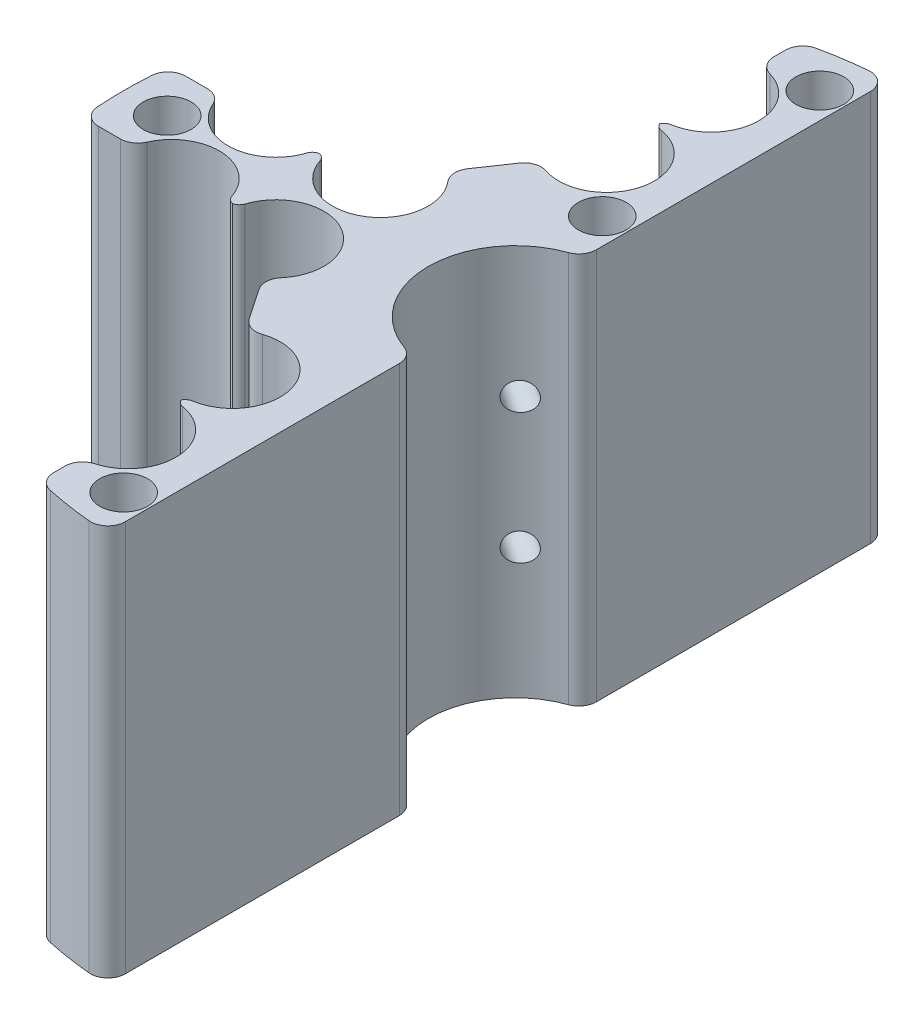
SolidWorks part; units mm, degrees
ref_plane "Front Plane" through (0, 0, 0) normal (0, 0, 1) x (1, 0, 0)
ref_plane "Top Plane" through (0, 0, 0) normal (0, 1, 0) x (1, 0, 0)
ref_plane "Right Plane" through (0, 0, 0) normal (1, 0, 0) x (0, 0, -1)
sketch "Sketch1" plane through (0, 0, 0) normal (0, 1, 0) x (1, 0, 0)
  line L1 (0, 45) -> (47.41, 45)
  line L2 (0, 45) -> (0, -45)
  line L3 (0, -45) -> (47.41, -45)
  line L4 (47.41, 45) -> (47.41, -45)
  line L5 (0, 45) -> (-1, 45)
  line L6 (0, 45) -> (0, -46.0697)
  line L7 (0, -46.0697) -> (-1, -46.0697)
  line L8 (-1, 45) -> (-1, -46.0697)
  circle A0 centre (0, 0) radius 45
  circle A1 centre (0, 0) radius 10
extrude "Boss-Extrude1" add sketch "Sketch1" along normal blind 45 contours A1 L2 A0
sketch "Sketch2" plane through (0, 45, 0) normal (0, 1, 0) x (1, 0, 0)
  circle A0 centre (-40, 0) radius 2.75
  circle A1 centre (-5, 15) radius 2.75
  circle A2 centre (-5, 40) radius 2.75
  circle A3 centre (-5, -40) radius 2.75
extrude "Cut-Extrude1" cut sketch "Sketch2" against normal blind 45
sketch "Sketch3" plane through (0, 45, 0) normal (0, 1, 0) x (1, 0, 0)
  line L0 (-40, 0) -> (-27.5, 0)
  line L1 (-27.5, 0) -> (-27.5, 6)
  line L2 (-27.5, 6) -> (-33.5, 6)
  line L3 (-27.5, 6) -> (-21.5, 6)
  line L4 (-5, 15) -> (-5, 27.5)
  line L5 (-5, 27.5) -> (-11, 27.5)
  line L6 (-11, 27.5) -> (-11, 21.5)
  line L7 (-11, 27.5) -> (-11, 33.5)
  line L8 (-24.2, 0) -> (24.2, 0) construction
  circle A0 centre (-33.5, 6) radius 5.5
  circle A1 centre (-21.5, 6) radius 5.5
  circle A2 centre (-11, 21.5) radius 5.5
  circle A3 centre (-11, 33.5) radius 5.5
  circle A4 centre (-33.5, -6) radius 5.5
  circle A5 centre (-21.5, -6) radius 5.5
  circle A6 centre (-11, -33.5) radius 5.5
  circle A7 centre (-11, -21.5) radius 5.5
extrude "Cut-Extrude2" cut sketch "Sketch3" against normal blind 45
sketch "Sketch4" plane through (0, 45, 0) normal (0, 1, 0) x (1, 0, 0)
  line L0 (-40, 0) -> (-27.5, 0)
  line L1 (-24.2, 0) -> (24.2, 0) construction
  line L2 (-44.7214, -5) -> (-44.7214, -43.6348)
  line L3 (-27.5, 5) -> (-44.7214, 5)
  line L4 (-27.5, 5) -> (-22.1112, 5)
  line L5 (-22.1112, 5) -> (-21.3807, 6.1952)
  line L6 (-21.3807, 6.1952) -> (-11, 21.5)
  line L7 (-11, 21.5) -> (-11, 43.6348)
  line L8 (-22.1112, -5) -> (-21.3807, -6.1952)
  line L9 (-27.5, -5) -> (-44.7214, -5)
  line L10 (-27.5, -5) -> (-22.1112, -5)
  line L11 (-21.3807, -6.1952) -> (-11, -21.5)
  line L12 (-11, -21.5) -> (-11, -43.6348)
  line L13 (-44.7214, -43.6348) -> (-11, -43.6348)
  line L14 (-11, 43.6348) -> (-44.7214, 43.6348)
  line L15 (-44.7214, 43.6348) -> (-44.7214, 5)
  arc A0 (-1, 44.9889) -> (-1, -44.9889) centre (0, 0) ccw construction
  circle M13 centre (-11, -33.5) radius 5.5
  circle M14 centre (-33.5, -6) radius 5.5
  circle M15 centre (-21.5, -6) radius 5.5
  circle M16 centre (-11, -21.5) radius 5.5
  arc M23 (-1, 44.9889) -> (-1, -44.9889) centre (0, 0) ccw
  circle M25 centre (-33.5, 6) radius 5.5
  circle M26 centre (-21.5, 6) radius 5.5
  circle M27 centre (-11, 21.5) radius 5.5
  circle M28 centre (-11, 33.5) radius 5.5
extrude "Cut-Extrude3" cut sketch "Sketch4" against normal blind 45 contours L7 L3 L4 L6 M27 M28 M23 M25 M26 | L12 L11 L10 L9 M16 M15 M14 M23 M13
sketch "Sketch5" plane through (-17.5219, 0, -11.8844) normal (-0.8276, 0, -0.5613) x (-0.5613, 0, 0.8276)
  circle A0 centre (-2.2579, 30) radius 1.6
  circle A1 centre (-2.2579, 15) radius 1.6
extrude "Cut-Extrude5" cut sketch "Sketch5" against normal blind 15
sketch "Sketch6" plane through (-17.5219, 0, 11.8844) normal (-0.8276, 0, 0.5613) x (0.5613, 0, 0.8276)
  circle A0 centre (2.2579, 30) radius 1.6
  circle A1 centre (2.2579, 15) radius 1.6
extrude "Cut-Extrude6" cut sketch "Sketch6" against normal blind 15
fillet "Fillet1" radius 2 4 edges at (-14.0873, 22.5, -16.9482) (-18.4217, 22.5, -10.5578) (-14.0873, 22.5, 16.9482) (-18.4217, 22.5, 10.5578)
fillet "Fillet2" radius 1 4 edges at (-11, 22.5, 28) (-11, 22.5, 27) (-11, 22.5, -27) (-11, 22.5, -28)
fillet "Fillet3" radius 2 8 edges at (-38.9083, 22.5, 5) (-44.7214, 22.5, 5) (-44.7214, 22.5, -5) (-38.9083, 22.5, -5) (-11, 22.5, -43.6348) (-11, 22.5, 43.6348) (-11, 22.5, 39) (-11, 22.5, -39)
fillet "Fillet4" radius 1 4 edges at (-26.9083, 22.5, 5) (-28.0917, 22.5, 5) (-28.0917, 22.5, -5) (-26.9083, 22.5, -5)
sketch "Sketch7" plane through (0, 45, 0) normal (0, 1, 0) x (1, 0, 0)
  line L1 (-1, 44.9889) -> (-2, 44.9889)
  line L2 (-1, 44.9889) -> (-1, -47.4203)
  line L3 (-1, -47.4203) -> (-2, -47.4203)
  line L4 (-2, 44.9889) -> (-2, -47.4203)
extrude "Cut-Extrude7" cut sketch "Sketch7" against normal blind 45
fillet "Fillet8" radius 2 4 edges at (-2, 22.5, 44.9555) (-2, 22.5, -44.9555) (-2, 22.5, -9.798) (-2, 22.5, 9.798)
